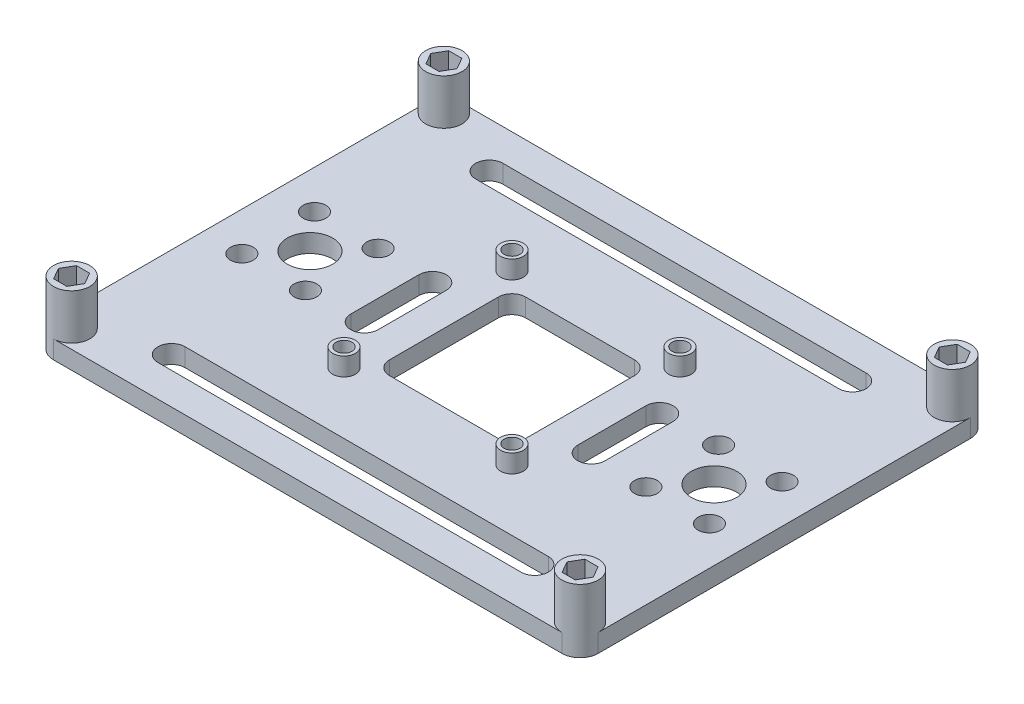
SolidWorks part; units mm, degrees
material "ABS"
ref_plane "Front Plane" through (0, 0, 0) normal (0, 0, 1) x (1, 0, 0)
ref_plane "Top Plane" through (0, 0, 0) normal (0, 1, 0) x (1, 0, 0)
ref_plane "Right Plane" through (0, 0, 0) normal (1, 0, 0) x (0, 0, -1)
sketch "Sketch1" plane through (0, 0, 0) normal (0, 1, 0) x (1, 0, 0)
  line L0 (0, 0) -> (0, 45) construction
  line L1 (-60, -45) -> (60, -45)
  line L2 (-60, -45) -> (-60, 45)
  line L3 (-60, 45) -> (60, 45)
  line L4 (60, -45) -> (60, 45)
  line L5 (-60, -45) -> (60, 45) construction
  line L6 (-60, 45) -> (60, -45) construction
  line L7 (-60, -13) -> (-29, -13)
  line L8 (-60, -13) -> (-60, 13)
  line L9 (-60, 13) -> (-29, 13)
  line L10 (-29, -13) -> (-29, 13)
  line L11 (-60, -13) -> (-29, 13) construction
  line L12 (-60, 13) -> (-29, -13) construction
  line L17 (-51.5, -8) -> (-37.5, 8) construction
  line L18 (-51.5, 8) -> (-37.5, -8) construction
  line L23 (60, 13) -> (29, 13)
  line L24 (29, -13) -> (29, 13)
  line L25 (60, -13) -> (29, -13)
  line L26 (60, -13) -> (60, 13)
  circle A0 centre (-44.5, 0) radius 5
  circle A1 centre (-37.5, 8) radius 2.5
  circle A2 centre (-51.5, 8) radius 2.5
  circle A3 centre (-51.5, -8) radius 2.5
  circle A4 centre (-37.5, -8) radius 2.5
  circle A5 centre (51.5, 8) radius 2.5
  circle A6 centre (37.5, 8) radius 2.5
  circle A7 centre (37.5, -8) radius 2.5
  circle A8 centre (51.5, -8) radius 2.5
  circle A9 centre (44.5, 0) radius 5
  point P0 (0, 0)
  point P6 (-44.5, 0)
  point P12 (-60, 0)
  point P22 (0, 0)
  dimension "D4" = 10
  dimension "D7" = 5
  dimension "D8" = 5
  dimension "D9" = 5
  dimension "D10" = 5
  dimension "D1" = 31
  dimension "D2" = 26
  dimension "D3" = 15.5
  dimension "D5" = 14
  dimension "D6" = 16
  dimension "D13" = 120
  dimension "D14" = 90
extrude "Boss-Extrude1" add sketch "Sketch1" along normal blind 4 contours L4 L25 L24 L23 L3 L2 L9 L10 L7 L1 | L7 L10 L9 L2 A4 A3 A2 A1 A0 | L25 L4 L23 L24 A8 A6 A5 A7 A9 region at (0, 0, 0) region at (-59.5954, 0, 0) region at (44.5, 0, 12.5954)
fillet "Fillet1" radius 4 4 edges at (-60, 2, 45) (-60, 2, -45) (60, 2, -45) (60, 2, 45)
sketch "Sketch2" plane through (0, 4, 0) normal (0, 1, 0) x (1, 0, 0)
  line L0 (-60, -41) -> (-60, 41) construction
  line L1 (-56, 45) -> (56, 45) construction
  line L3 (-53.1, 41) -> (-54.55, 43.5115)
  line L4 (-54.55, 43.5115) -> (-57.45, 43.5115)
  line L5 (-57.45, 43.5115) -> (-58.9, 41)
  line L6 (-58.9, 41) -> (-57.45, 38.4885)
  line L7 (-57.45, 38.4885) -> (-54.55, 38.4885)
  line L8 (-54.55, 38.4885) -> (-53.1, 41)
  circle A1 centre (-56, 41) radius 2.5115 construction
  circle A2 centre (-56, 41) radius 4
  dimension "D1" = 4
  dimension "D3" = 4
extrude "Boss-Extrude2" add sketch "Sketch2" along normal blind 10
mirror "Mirror1" about plane through (0, 0, 0) normal (0, 0, 1) of "Boss-Extrude2"
mirror "Mirror2" about plane through (0, 0, 0) normal (1, 0, 0) of "Mirror1"
sketch "Sketch3" plane through (0, 4, 0) normal (0, 1, 0) x (1, 0, 0)
  circle A0 centre (-56, 41) radius 1.75
  dimension "D1" = 3.5
extrude "Cut-Extrude1" cut sketch "Sketch3" against normal blind 4
mirror "Mirror3" about plane through (0, 0, 0) normal (1, 0, 0) of "Cut-Extrude1"
mirror "Mirror4" about plane through (0, 0, 0) normal (0, 0, 1) of "Mirror3"
sketch "Sketch4" plane through (0, 4, 0) normal (0, 1, 0) x (1, 0, 0)
  line L0 (0, -7.7) -> (0, 7.7) construction
  line L5 (-22.5, -22.5) -> (22.5, 22.5) construction
  line L6 (-22.5, 22.5) -> (22.5, -22.5) construction
  line L7 (-7.7, 0) -> (7.7, 0) construction
  circle A0 centre (-18.5, 18.5) radius 2.5
  circle A1 centre (18.5, 18.5) radius 2.5
  circle A2 centre (18.5, -18.5) radius 2.5
  circle A3 centre (-18.5, -18.5) radius 2.5
  point P0 (0, 0)
  dimension "D5" = 5
  dimension "D1" = 45
  dimension "D2" = 45
  dimension "D3" = 18.5
  dimension "D4" = 18.5
extrude "Boss-Extrude3" add sketch "Sketch4" along normal blind 4
sketch "Sketch5" plane through (0, 8, 0) normal (0, 1, 0) x (1, 0, 0)
  circle A0 centre (-18.5, 18.5) radius 1.75
  dimension "D1" = 3.5
extrude "Cut-Extrude2" cut sketch "Sketch5" against normal blind 10
mirror "Mirror5" about plane through (0, 0, 0) normal (1, 0, 0) of "Cut-Extrude2"
mirror "Mirror6" about plane through (0, 0, 0) normal (0, 0, 1) of "Mirror5"
sketch "Sketch6" plane through (0, 4, 0) normal (0, 1, 0) x (1, 0, 0)
  line L0 (-25, -7.5) -> (-25, 7.5) construction
  line L1 (-12, -15) -> (12, -15)
  line L2 (-15, -12) -> (-15, 12)
  line L3 (-12, 15) -> (12, 15)
  line L4 (15, -12) -> (15, 12)
  line L5 (-15, -15) -> (15, 15) construction
  line L6 (-15, 15) -> (15, -15) construction
  line L7 (-28, -7.5) -> (-28, 7.5)
  line L8 (-22, -7.5) -> (-22, 7.5)
  line L9 (0, -7.7) -> (0, 7.7) construction
  line L10 (25, -7.5) -> (25, 7.5) construction
  line L11 (28, -7.5) -> (28, 7.5)
  line L12 (22, -7.5) -> (22, 7.5)
  line L13 (-40, 35) -> (40, 35) construction
  line L14 (-40, 38) -> (40, 38)
  line L15 (-40, 32) -> (40, 32)
  line L16 (-7.7, 0) -> (7.7, 0) construction
  line L17 (-40, -35) -> (40, -35) construction
  line L18 (-40, -38) -> (40, -38)
  line L19 (-40, -32) -> (40, -32)
  arc A0 (-28, -7.5) -> (-22, -7.5) centre (-25, -7.5) ccw
  arc A1 (-22, 7.5) -> (-28, 7.5) centre (-25, 7.5) ccw
  arc A2 (28, -7.5) -> (22, -7.5) centre (25, -7.5) cw
  arc A3 (22, 7.5) -> (28, 7.5) centre (25, 7.5) cw
  arc A4 (-40, 38) -> (-40, 32) centre (-40, 35) ccw
  arc A5 (40, 32) -> (40, 38) centre (40, 35) ccw
  arc A6 (-40, -38) -> (-40, -32) centre (-40, -35) cw
  arc A7 (40, -32) -> (40, -38) centre (40, -35) cw
  arc A8 (15, 12) -> (12, 15) centre (12, 12) ccw
  arc A9 (12, -15) -> (15, -12) centre (12, -12) ccw
  arc A10 (-12, -15) -> (-15, -12) centre (-12, -12) cw
  arc A11 (-15, 12) -> (-12, 15) centre (-12, 12) cw
  point P0 (0, 0)
  point P8 (-25, 0)
  point P18 (25, 0)
  point P23 (0, 35)
  point P29 (0, 0)
  point P34 (0, -35)
  dimension "D5" = 3
  dimension "D7" = 3
  dimension "D9" = 3
  dimension "D1" = 30
  dimension "D2" = 30
  dimension "D3" = 25
  dimension "D4" = 15
  dimension "D6" = 35
  dimension "D8" = 80
extrude "Cut-Extrude3" cut sketch "Sketch6" against normal blind 10
